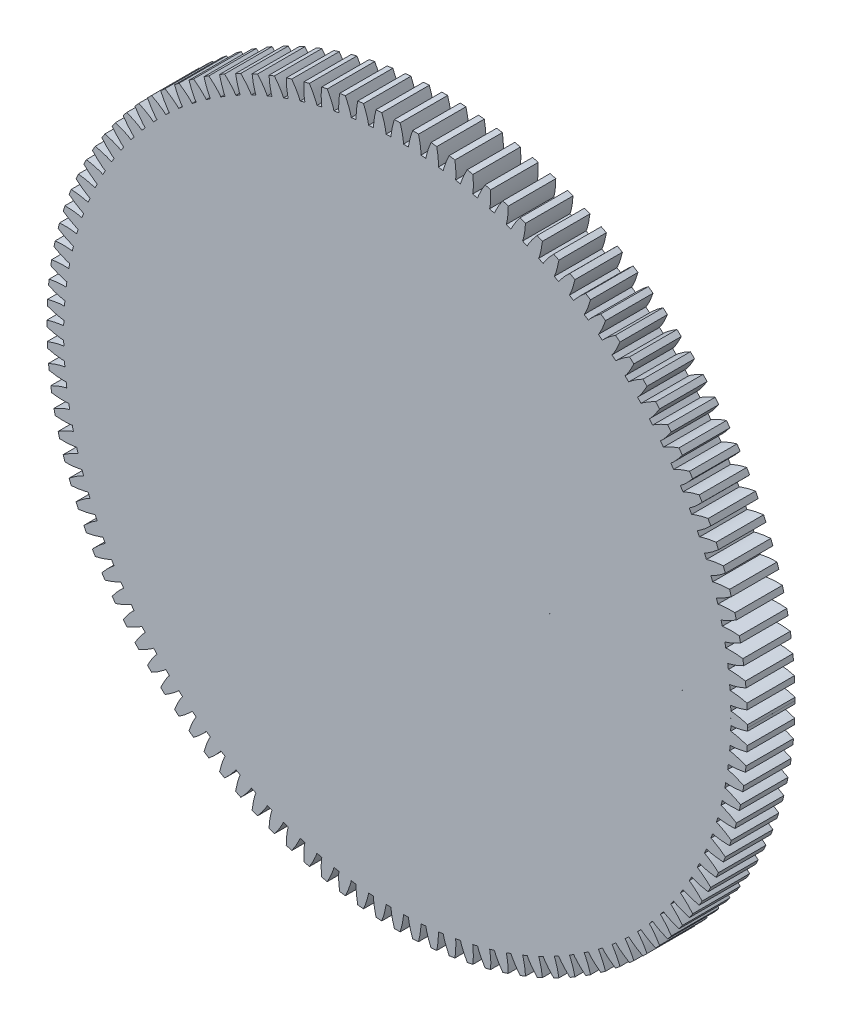
SolidWorks part; units mm, degrees
material "Brass"
ref_plane "Front Plane" through (0, 0, 0) normal (0, 0, 1) x (1, 0, 0)
ref_plane "Top Plane" through (0, 0, 0) normal (0, 1, 0) x (1, 0, 0)
ref_plane "Right Plane" through (0, 0, 0) normal (1, 0, 0) x (0, 0, -1)
sketch "Sketch1" plane through (0, 0, 0) normal (0, 1, 0) x (1, 0, 0)
  line L0 (0, 0) -> (51.6467, 0)
  line L1 (51.6467, 0) -> (51.6467, -7)
  line L2 (51.6467, -7) -> (0, -7)
  line L3 (0, -7) -> (0, 0)
  line L4 (0, -1) -> (0, -6) construction
revolve "Revolve1" add sketch "Sketch1" angle 360 about L4
sketch "Sketch2" plane through (0, 0, 0) normal (0, 0, 1) x (1, 0, 0)
  spline S0 degree 4 poles (49.1734, 0.9164) (49.1838, 0.9166) (49.2037, 0.9164) (49.236, 0.9157) (49.2811, 0.9138) (49.3345, 0.9109) (49.3975, 0.9065) (49.4669, 0.9007) (49.5426, 0.8933) (49.6181, 0.8849) (49.6937, 0.8757) (49.769, 0.8656) (49.8604, 0.8525) (49.9703, 0.8355) (50.099, 0.8136) (50.2454, 0.7864) (50.3952, 0.7562) (50.5429, 0.7245) (50.6927, 0.69) (50.8381, 0.655) (50.9896, 0.6161) (51.1298, 0.579) (51.2875, 0.5348) (51.415, 0.4982) (51.584, 0.4471) (51.6841, 0.416) (51.8014, 0.3786) (51.8537, 0.3614) (51.8859, 0.3509) knots 0 0 0 0 0 0.015084 0.028532 0.04661 0.064855 0.092111 0.119476 0.146842 0.174209 0.201575 0.228941 0.256307 0.307035 0.361767 0.4165 0.471232 0.525964 0.580697 0.635429 0.690161 0.744894 0.799626 0.854358 0.909091 0.954545 1 1 1 1 1 construction
  spline S1 degree 4 poles (49.1734, 0.9164) (49.1838, 0.9166) (49.2037, 0.9164) (49.236, 0.9157) (49.2811, 0.9138) (49.3345, 0.9109) (49.3975, 0.9065) (49.4669, 0.9007) (49.5426, 0.8933) (49.6181, 0.8849) (49.6937, 0.8757) (49.769, 0.8656) (49.8604, 0.8525) (49.9703, 0.8355) (50.099, 0.8136) (50.2454, 0.7864) (50.3952, 0.7562) (50.5429, 0.7245) (50.6927, 0.69) (50.8381, 0.655) (50.9896, 0.6161) (51.1298, 0.579) (51.2875, 0.5348) (51.415, 0.4982) (51.5474, 0.4582) (51.6119, 0.4383) (51.6449, 0.428) knots 0 0 0 0 0 0.015084 0.028532 0.04661 0.064855 0.092111 0.119476 0.146842 0.174209 0.201575 0.228941 0.256307 0.307035 0.361767 0.4165 0.471232 0.525964 0.580697 0.635429 0.690161 0.744894 0.799626 0.854358 0.909091 0.909091 0.909091 0.909091 0.909091
  spline S2 degree 4 poles (49.1539, 1.6583) (49.1644, 1.6588) (49.1842, 1.66) (49.2165, 1.6624) (49.2614, 1.6666) (49.3146, 1.6723) (49.3773, 1.68) (49.4463, 1.6894) (49.5214, 1.7008) (49.5965, 1.7131) (49.6714, 1.7263) (49.7461, 1.7403) (49.8367, 1.7581) (49.9455, 1.7809) (50.0729, 1.8095) (50.2177, 1.8443) (50.3657, 1.8823) (50.5116, 1.9217) (50.6594, 1.964) (50.8027, 2.0066) (50.952, 2.0533) (51.09, 2.0977) (51.2452, 2.1502) (51.3706, 2.1933) (51.5367, 2.2532) (51.635, 2.2895) (51.7503, 2.333) (51.8016, 2.3529) (51.8332, 2.3651) knots 0 0 0 0 0 0.015084 0.028532 0.04661 0.064855 0.092111 0.119476 0.146842 0.174209 0.201575 0.228941 0.256307 0.307035 0.361767 0.4165 0.471232 0.525964 0.580697 0.635429 0.690161 0.744894 0.799626 0.854358 0.909091 0.954545 1 1 1 1 1 construction
  spline S3 degree 4 poles (49.1539, 1.6583) (49.1644, 1.6588) (49.1842, 1.66) (49.2165, 1.6624) (49.2614, 1.6666) (49.3146, 1.6723) (49.3773, 1.68) (49.4463, 1.6894) (49.5214, 1.7008) (49.5965, 1.7131) (49.6714, 1.7263) (49.7461, 1.7403) (49.8367, 1.7581) (49.9455, 1.7809) (50.0729, 1.8095) (50.2177, 1.8443) (50.3657, 1.8823) (50.5116, 1.9217) (50.6594, 1.964) (50.8027, 2.0066) (50.952, 2.0533) (51.09, 2.0977) (51.2452, 2.1502) (51.3706, 2.1933) (51.5007, 2.2403) (51.5641, 2.2634) (51.5965, 2.2754) knots 0 0 0 0 0 0.015084 0.028532 0.04661 0.064855 0.092111 0.119476 0.146842 0.174209 0.201575 0.228941 0.256307 0.307035 0.361767 0.4165 0.471232 0.525964 0.580697 0.635429 0.690161 0.744894 0.799626 0.854358 0.909091 0.909091 0.909091 0.909091 0.909091
  spline S4 degree 4 poles (49.152, 1.7331) (49.1521, 1.7275) (49.1524, 1.7162) (49.1528, 1.7032) (49.1537, 1.6661) (49.1542, 1.6496) (49.1554, 1.6026) (49.1561, 1.5744) (49.1572, 1.5339) (49.158, 1.5022) (49.1589, 1.4673) (49.1598, 1.4358) (49.1606, 1.4032) (49.1615, 1.3704) (49.1623, 1.3377) (49.1632, 1.3038) (49.1641, 1.2685) (49.1651, 1.2321) (49.1661, 1.1947) (49.1671, 1.1572) (49.168, 1.1226) (49.1689, 1.0853) (49.1698, 1.0523) (49.1709, 1.0096) (49.1717, 0.9804) (49.1731, 0.927) (49.1735, 0.9094) (49.1745, 0.8714) (49.1749, 0.857) (49.1752, 0.847) (49.1753, 0.8418) knots 0 0 0 0 0 0.022088 0.044177 0.083333 0.119319 0.159813 0.201093 0.243304 0.280291 0.314751 0.350761 0.388774 0.424594 0.463227 0.497138 0.541352 0.583276 0.626202 0.666552 0.706902 0.743676 0.7856 0.828955 0.87417 0.916667 0.958835 0.979418 1 1 1 1 1 construction
  spline S5 degree 4 poles (49.1539, 1.6583) (49.1541, 1.6517) (49.1545, 1.6378) (49.1554, 1.6026) (49.1561, 1.5744) (49.1572, 1.5339) (49.158, 1.5022) (49.1589, 1.4673) (49.1598, 1.4358) (49.1606, 1.4032) (49.1615, 1.3704) (49.1623, 1.3377) (49.1632, 1.3038) (49.1641, 1.2685) (49.1651, 1.2321) (49.1661, 1.1947) (49.1671, 1.1572) (49.168, 1.1226) (49.1689, 1.0853) (49.1698, 1.0523) (49.1709, 1.0096) (49.1717, 0.9804) (49.1727, 0.94) (49.1732, 0.9243) (49.1734, 0.9164) knots 0.083333 0.083333 0.083333 0.083333 0.083333 0.119319 0.159813 0.201093 0.243304 0.280291 0.314751 0.350761 0.388774 0.424594 0.463227 0.497138 0.541352 0.583276 0.626202 0.666552 0.706902 0.743676 0.7856 0.828955 0.87417 0.916667 0.916667 0.916667 0.916667 0.916667
  spline S6 degree 4 poles (50.8043, 0.4211) (50.864, 0.4216) (50.9794, 0.4225) (51.1316, 0.4238) (51.5629, 0.4274) (51.7496, 0.4289) (52.3065, 0.4335) (52.6262, 0.4362) (53.0785, 0.4399) (53.4484, 0.443) (53.8676, 0.4465) (54.2464, 0.4496) (54.6546, 0.453) (55.0383, 0.4562) (55.4322, 0.4594) (55.8223, 0.4627) (56.2055, 0.4658) (56.6028, 0.4691) (56.9958, 0.4724) (57.4001, 0.4757) (57.7912, 0.479) (58.2102, 0.4825) (58.5784, 0.4855) (59.0365, 0.4893) (59.3484, 0.4919) (59.8904, 0.4964) (60.0774, 0.4979) (60.499, 0.5014) (60.6501, 0.5027) (60.7751, 0.5037) (60.8382, 0.5042) knots 0 0 0 0 0 0.020582 0.041165 0.083333 0.123922 0.164487 0.203919 0.245641 0.283463 0.324863 0.363448 0.401438 0.443624 0.479586 0.519794 0.557378 0.596758 0.637386 0.678142 0.716036 0.757316 0.79719 0.837516 0.878097 0.916667 0.955572 0.977786 1 1 1 1 1 construction
  spline S7 degree 4 poles (51.6449, 0.428) (51.7297, 0.4287) (51.8939, 0.4301) (52.3065, 0.4335) (52.6262, 0.4362) (53.0785, 0.4399) (53.4484, 0.443) (53.8676, 0.4465) (54.2464, 0.4496) (54.6546, 0.453) (55.0383, 0.4562) (55.4322, 0.4594) (55.8223, 0.4627) (56.2055, 0.4658) (56.6028, 0.4691) (56.9958, 0.4724) (57.4001, 0.4757) (57.7912, 0.479) (58.2102, 0.4825) (58.5784, 0.4855) (59.0365, 0.4893) (59.3484, 0.4919) (59.7573, 0.4953) (59.9173, 0.4966) (59.9978, 0.4973) knots 0.083333 0.083333 0.083333 0.083333 0.083333 0.123922 0.164487 0.203919 0.245641 0.283463 0.324863 0.363448 0.401438 0.443624 0.479586 0.519794 0.557378 0.596758 0.637386 0.678142 0.716036 0.757316 0.79719 0.837516 0.878097 0.916667 0.916667 0.916667 0.916667 0.916667
  spline S8 degree 4 poles (59.9992, 0.2811) (59.9991, 0.2966) (59.999, 0.3264) (59.9988, 0.3667) (59.998, 0.4759) (59.9976, 0.5237) (59.9963, 0.6646) (59.9953, 0.7445) (59.9938, 0.8601) (59.9923, 0.9543) (59.9905, 1.0614) (59.9887, 1.1607) (59.9866, 1.2646) (59.9844, 1.3658) (59.9819, 1.4686) (59.9794, 1.5706) (59.9766, 1.6727) (59.9736, 1.7754) (59.9706, 1.8766) (59.9672, 1.9805) (59.9639, 2.0797) (59.96, 2.1868) (59.9566, 2.2809) (59.952, 2.3964) (59.9488, 2.4763) (59.9428, 2.617) (59.9407, 2.6648) (59.9358, 2.7739) (59.9338, 2.8142) (59.9324, 2.844) (59.9317, 2.8594) knots 0 0 0 0 0 0.020959 0.041918 0.083333 0.123016 0.162698 0.202381 0.242063 0.281746 0.321429 0.361111 0.400794 0.440476 0.480159 0.519841 0.559524 0.599206 0.638889 0.678571 0.718254 0.757937 0.797619 0.837302 0.876984 0.916667 0.958082 0.979041 1 1 1 1 1 construction
  spline S9 degree 4 poles (59.9978, 0.4973) (59.9976, 0.5186) (59.9973, 0.5601) (59.9963, 0.6646) (59.9953, 0.7445) (59.9938, 0.8601) (59.9923, 0.9543) (59.9905, 1.0614) (59.9887, 1.1607) (59.9866, 1.2646) (59.9844, 1.3658) (59.9819, 1.4686) (59.9794, 1.5706) (59.9766, 1.6727) (59.9736, 1.7754) (59.9706, 1.8766) (59.9672, 1.9805) (59.9639, 2.0797) (59.96, 2.1868) (59.9566, 2.2809) (59.952, 2.3964) (59.9488, 2.4763) (59.9444, 2.5807) (59.9426, 2.6222) (59.9416, 2.6434) knots 0.083333 0.083333 0.083333 0.083333 0.083333 0.123016 0.162698 0.202381 0.242063 0.281746 0.321429 0.361111 0.400794 0.440476 0.480159 0.519841 0.559524 0.599206 0.638889 0.678571 0.718254 0.757937 0.797619 0.837302 0.876984 0.916667 0.916667 0.916667 0.916667 0.916667
  spline S10 degree 4 poles (60.7813, 2.6805) (60.7233, 2.6779) (60.6112, 2.673) (60.4593, 2.6663) (60.0264, 2.6472) (59.8505, 2.6394) (59.3125, 2.6157) (59.0208, 2.6028) (58.6061, 2.5846) (58.2603, 2.5693) (57.8595, 2.5516) (57.496, 2.5356) (57.0992, 2.5181) (56.7297, 2.5018) (56.3678, 2.4858) (56.0013, 2.4697) (55.6349, 2.4535) (55.2589, 2.4369) (54.8708, 2.4198) (54.4874, 2.4029) (54.084, 2.3851) (53.7043, 2.3684) (53.2954, 2.3503) (52.937, 2.3345) (52.5215, 2.3162) (52.2196, 2.3029) (51.696, 2.2798) (51.481, 2.2703) (51.015, 2.2498) (50.8906, 2.2443) (50.7566, 2.2384) knots 0 0 0 0 0 0.02008 0.040161 0.083333 0.123261 0.159319 0.197812 0.233027 0.26907 0.309878 0.349805 0.383268 0.424652 0.459253 0.493239 0.530412 0.57034 0.610222 0.64719 0.685114 0.729048 0.765971 0.80369 0.838967 0.877741 0.916667 0.958333 1 1 1 1 1 construction
  spline S11 degree 4 poles (59.9416, 2.6434) (59.8583, 2.6398) (59.7031, 2.6329) (59.3125, 2.6157) (59.0208, 2.6028) (58.6061, 2.5846) (58.2603, 2.5693) (57.8595, 2.5516) (57.496, 2.5356) (57.0992, 2.5181) (56.7297, 2.5018) (56.3678, 2.4858) (56.0013, 2.4697) (55.6349, 2.4535) (55.2589, 2.4369) (54.8708, 2.4198) (54.4874, 2.4029) (54.084, 2.3851) (53.7043, 2.3684) (53.2954, 2.3503) (52.937, 2.3345) (52.5215, 2.3162) (52.2196, 2.3029) (51.8371, 2.286) (51.6777, 2.279) (51.5965, 2.2754) knots 0.083333 0.083333 0.083333 0.083333 0.083333 0.123261 0.159319 0.197812 0.233027 0.26907 0.309878 0.349805 0.383268 0.424652 0.459253 0.493239 0.530412 0.57034 0.610222 0.64719 0.685114 0.729048 0.765971 0.80369 0.838967 0.877741 0.916667 0.916667 0.916667 0.916667 0.916667
extrude "Cut-Extrude2" cut sketch "Sketch2" against normal blind 8 and the other way blind 8
ref_axis "Axis1" through (0, 0, -0.35) along (0, 0, 1)
pattern_circular "CirPattern2" count 120 over 360 about axis through (0, 0, 7) along (0, 0, -1) of "Cut-Extrude2"
equation "\"TrigProbe\"= cos(60)"
equation "\"SqrProbe\"= sqr(2)"
equation "\"AtnProbe\"= atn(1)"
equation "\"ToothCount\" = 120"
equation "\"DP\"= 30"
equation "\"PA\"= 14.5"
equation "\"PArad\"= \"PA\" * 3.14159265358979 / 180"
equation "\"Rb\"= \"ToothCount\" / \"DP\" * cos(\"PA\") / 2"
equation "\"Ra\"= (\"ToothCount\" + 2) / \"DP\" / 2"
equation "\"Tmax\"= sqr(\"Ra\" * \"Ra\" / (\"Rb\" * \"Rb\") - 1)"
equation "\"Delta\"= 3.14159265358979 / (2 * \"ToothCount\") + tan(\"PA\") - \"PArad\""
equation "\"Gamma\"= 2 * 3.14159265358979 / \"ToothCount\""
equation "\"ThetaL\"= atn(\"Tmax\") * 3.14159265358979 / 180 - \"Tmax\" + \"Delta\""
equation "\"ThetaU\"= \"Tmax\" - atn(\"Tmax\") * 3.14159265358979 / 180 - \"Delta\" + \"Gamma\""
equation "\"D1@Sketch1\" = \"Ra\""
equation "\"D1@CirPattern2\" = \"ToothCount\""
